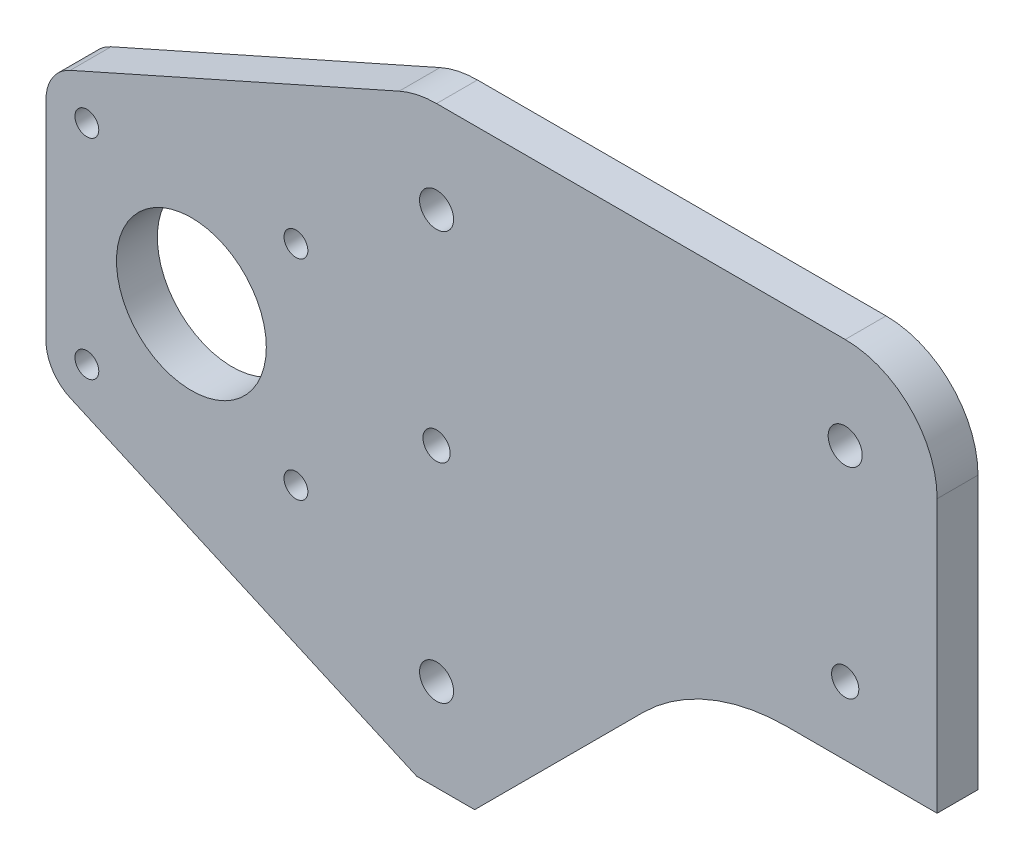
SolidWorks part; units mm, degrees
ref_plane "Plano frontal" through (0, 0, 0) normal (0, 0, 1) x (1, 0, 0)
ref_plane "Plano superior" through (0, 0, 0) normal (0, 1, 0) x (1, 0, 0)
ref_plane "Plano direito" through (0, 0, 0) normal (1, 0, 0) x (0, 0, -1)
sketch "Esboço1" plane through (0, 0, 0) normal (0, 0, 1) x (1, 0, 0)
  line L1 (-30, 30) -> (30, 30) construction
  line L2 (-30, 30) -> (-30, -30) construction
  line L3 (-30, -30) -> (30, -30) construction
  line L4 (30, 30) -> (30, -30) construction
  line L5 (-30, 30) -> (30, -30) construction
  line L6 (-30, -30) -> (30, 30) construction
  line L7 (-24.4081, -43.5) -> (0.3051, -18.7868)
  line L8 (30, 43.5) -> (-30, 43.5)
  line L18 (-81.3491, 15.3491) -> (-50.6509, 15.3491) construction
  line L19 (-81.3491, 15.3491) -> (-81.3491, -15.3491) construction
  line L20 (-81.3491, -15.3491) -> (-50.6509, -15.3491) construction
  line L21 (-50.6509, 15.3491) -> (-50.6509, -15.3491) construction
  line L22 (-81.3491, 15.3491) -> (-50.6509, -15.3491) construction
  line L23 (-81.3491, -15.3491) -> (-50.6509, 15.3491) construction
  line L27 (-87.3491, 15.3491) -> (-87.3491, -15.3491)
  line L28 (-32.9246, -43.5) -> (-83.7916, -20.8294)
  line L29 (-35.4906, 42.333) -> (-83.7894, 20.8304)
  line L30 (0, 0) -> (43.5, 0) construction
  line L31 (21.5183, -10) -> (43.5, -10)
  line L32 (0, 0) -> (43.5, 0) construction
  line L33 (43.5, 30) -> (43.5, -10)
  line L34 (-24.4081, -43.5) -> (-32.9246, -43.5)
  line L35 (0, -10) -> (43.5, -10) construction
  circle A0 centre (-30, 30) radius 2.5
  circle A1 centre (-30, -30) radius 2.5
  circle A2 centre (30, 30) radius 2.5
  arc A3 (-30, 43.5) -> (-35.4906, 42.333) centre (-30, 30) ccw
  arc A5 (43.5, 30) -> (30, 43.5) centre (30, 30) ccw
  circle A6 centre (-81.3491, 15.3491) radius 1.75
  circle A7 centre (30, 30) radius 13.5 construction
  circle A9 centre (-30, 30) radius 13.5 construction
  circle A10 centre (-50.6509, 15.3491) radius 1.75
  circle A11 centre (-50.6509, -15.3491) radius 1.75
  circle A12 centre (-81.3491, -15.3491) radius 1.75
  circle A15 centre (-66, 0) radius 11
  arc A16 (-83.7894, 20.8304) -> (-87.3491, 15.3491) centre (-81.3491, 15.3491) ccw
  arc A17 (-87.3491, -15.3491) -> (-83.7916, -20.8294) centre (-81.3491, -15.3491) ccw
  arc A18 (21.5183, -10) -> (0.3051, -18.7868) centre (21.5183, -40) ccw
  circle A19 centre (-30, 0) radius 2
  circle A20 centre (0, 0) radius 2 construction
  circle A21 centre (30, 0) radius 2
  point P0 (0, 0)
  point P12 (-30, -30)
  point P13 (-20, 22.5)
  point P15 (-20, -22.5)
  point P20 (44, 0)
  point P23 (-66, 0)
  point P34 (-81.0386, -15.474)
  point P36 (-81.0386, 15.2242)
  point P37 (-74.2886, -15.474)
  point P43 (-74.2886, 15.2242)
  dimension "D3" = 5
  dimension "D6" = 3.5
  dimension "D8" = 22
  dimension "D11" = 30
  dimension "D12" = 4
  dimension "D1" = 60
  dimension "D2" = 60
  dimension "D5" = 60
  dimension "D9" = 36
  dimension "D7" = 6
  dimension "D13" = 30
  dimension "D4" = 11
  dimension "D10" = 10
extrude "Ressalto-extrusão1" add sketch "Esboço1" along normal blind 6
ref_axis "Eixo1" through (-30, 30, 6) along (0, 0, -1)
ref_axis "Eixo2" through (30, 30, 6) along (0, 0, -1)
ref_axis "Eixo3" through (-30, -30, 6) along (0, 0, -1)
ref_plane "Plano1" through (-30, 0, 0) normal (1, 0, 0) x (0, 0, -1)
ref_plane "Plano2" through (30, 0, 0) normal (1, 0, 0) x (0, 0, -1)
ref_plane "Plano3" through (0, 0, 0) normal (1, 0, 0) x (0, 0, -1)
ref_axis "Eixo4" through (30, 0, 6) along (0, 0, -1)
ref_axis "Eixo5" through (-30, 0, 6) along (0, 0, -1)
ref_plane "Plano4" through (0, 0, 0) normal (0, -1, 0) x (-1, 0, 0)
ref_axis "Eixo6" through (-50.6509, 15.3491, 6) along (0, 0, -1)
ref_axis "Eixo7" through (-50.6509, -15.3491, 6) along (0, 0, -1)
ref_plane "Plano5" through (-50.6509, 0, 0) normal (1, 0, 0) x (0, 0, -1)
